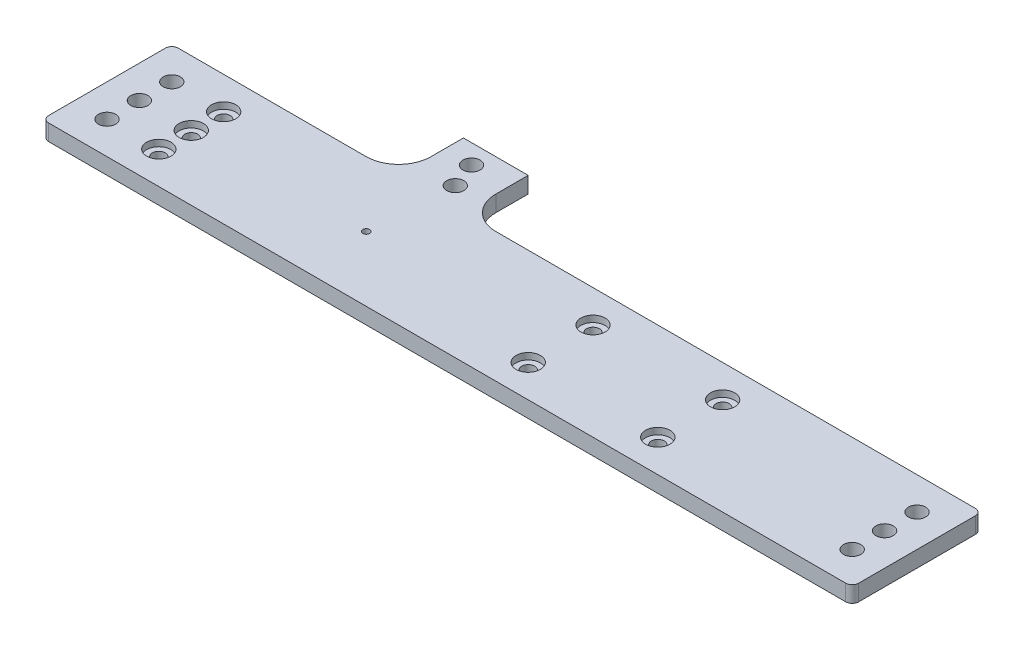
SolidWorks part; units mm, degrees
material "6061-T6 (SS)"
ref_plane "Front" through (0, 0, 0) normal (0, 0, 1) x (1, 0, 0)
ref_plane "Top" through (0, 0, 0) normal (0, 1, 0) x (1, 0, 0)
ref_plane "Right" through (0, 0, 0) normal (1, 0, 0) x (0, 0, -1)
sketch "Sketch1" plane through (0, 0, 0) normal (0, 1, 0) x (1, 0, 0)
  line L1 (-158.75, -25.4) -> (158.75, -25.4)
  line L2 (-158.75, -25.4) -> (-158.75, 25.4)
  line L3 (-158.75, 25.4) -> (158.75, 25.4)
  line L4 (158.75, -25.4) -> (158.75, 25.4)
  line L5 (-158.75, -25.4) -> (158.75, 25.4) construction
  line L6 (-158.75, 25.4) -> (158.75, -25.4) construction
  point P0 (0, 0)
  dimension "D1" = 50.8
  dimension "D2" = 317.5
extrude "Boss-Extrude1" add sketch "Sketch1" along normal blind 6.35
hole_wizard "CBORE for #10 Socket Head Cap Screw1" positions "Sketch2" profile "Sketch4" counterbore size "#10" standard "ANSI Inch" end condition through all
sketch "Sketch2" plane through (0, 6.35, 0) normal (0, 1, 0) x (1, 0, 0)
  line L2 (158.75, 25.4) -> (-158.75, 25.4) construction
  line L6 (-158.75, -25.4) -> (158.75, -25.4) construction
  line L8 (-158.75, 25.4) -> (-158.75, -25.4) construction
  line L12 (158.75, -25.4) -> (158.75, 25.4) construction
  line L15 (19.05, 12.7) -> (19.05, 25.4) construction
  line L17 (19.05, -12.7) -> (19.05, -25.4) construction
  line L18 (-125.73, -25.4) -> (-125.73, -12.7) construction
  line L20 (-125.73, 0) -> (-125.73, 12.7) construction
  line L21 (-125.73, 12.7) -> (-125.73, 25.4) construction
  line L22 (-125.73, 0) -> (-125.73, -12.7) construction
  point P64 (19.05, 12.7)
  point P66 (69.85, 12.7)
  point P68 (19.05, -12.7)
  point P70 (69.85, -12.7)
  point P92 (-125.73, 12.7)
  point P94 (-125.73, 0)
  point P102 (-125.73, -12.7)
  dimension "D2" = 50.8
  dimension "D3" = 25.4
  dimension "D4" = 88.9
  dimension "D5" = 33.02
sketch "Sketch4" plane through (-125.73, 6.35, 12.7) normal (1, 0, 0) x (0, 0, 1)
  line L0 (0, 0) -> (0, 6.35)
  line L1 (0, 6.35) -> (2.5527, 6.35)
  line L3 (2.5527, 6.35) -> (2.5527, 2.54)
  line L4 (2.5527, 2.54) -> (4.7625, 2.54)
  line L5 (4.7625, 2.54) -> (4.7625, 0)
  line L7 (4.7625, 0) -> (0, 0)
  line L11 (0, -6.35) -> (0, 107.95) construction
  dimension "Thru Hole Dia." = 5.1054
  dimension "Thru Hole Depth" = 6.35
  dimension "C'Bore Dia." = 9.525
  dimension "C'Bore Depth" = 2.54
sketch "Sketch7" plane through (0, 0, 0) normal (0, -1, 0) x (1, 0, 0)
  line L0 (-146.05, 25.4) -> (-146.05, 12.7) construction
  line L1 (-158.75, 25.4) -> (158.75, 25.4) construction
  line L2 (-146.05, 12.7) -> (-146.05, 0) construction
  line L3 (-146.05, 0) -> (-146.05, -12.7) construction
  line L4 (-146.05, -12.7) -> (-146.05, -25.4) construction
  line L5 (158.75, -25.4) -> (-158.75, -25.4) construction
  line L7 (-158.75, -25.4) -> (-158.75, 25.4) construction
  line L8 (146.05, 25.4) -> (146.05, 12.7) construction
  line L9 (146.05, 12.7) -> (146.05, 0) construction
  line L10 (146.05, 0) -> (146.05, -12.7) construction
  line L11 (146.05, -12.7) -> (146.05, -25.4) construction
  line L13 (158.75, 25.4) -> (158.75, -25.4) construction
  point P0 (-146.05, 12.7)
  point P2 (-146.05, 0)
  point P4 (-146.05, -12.7)
  point P6 (146.05, 12.7)
  point P8 (146.05, 0)
  point P10 (146.05, -12.7)
  dimension "D1" = 12.7
  dimension "D2" = 12.7
hole_wizard "1/4 Clearance Hole2" positions "Sketch7" profile "Sketch6" hole size "1/4" standard "ANSI Inch" end condition through all
sketch "Sketch6" plane through (-146.05, 0, 12.7) normal (1, 0, 0) x (0, 0, -1)
  line L0 (0, 0) -> (0, 6.35)
  line L1 (0, 6.35) -> (3.3782, 6.35)
  line L2 (3.3782, 6.35) -> (3.3782, 0)
  line L5 (3.3782, 0) -> (0, 0)
  line L11 (0, -6.35) -> (0, 107.95) construction
  dimension "Thru Hole Dia." = 6.7564
  dimension "Thru Hole Depth" = 6.35
sketch "Sketch10" plane through (0, 0, 0) normal (0, -1, 0) x (-1, 0, 0)
  line L0 (158.75, 25.4) -> (158.75, -25.4) construction
  point P0 (57.15, 0)
  dimension "D1" = 101.6
hole_wizard "#6-32 Tapped Hole1" positions "Sketch10" profile "Sketch9" tap size "#6-32" standard "ANSI Inch" end condition through all
sketch "Sketch9" plane through (-57.15, 0, 0) normal (1, 0, 0) x (0, 0, -1)
  line L0 (0, 0) -> (0, 6.35)
  line L1 (0, 6.35) -> (1.3525, 6.35)
  line L2 (1.3525, 6.35) -> (1.3525, 0)
  line L5 (1.3525, 0) -> (0, 0)
  line L11 (0, -6.35) -> (0, 107.95) construction
  dimension "Thru Tap Drill Dia." = 2.7051
  dimension "Thru Tap Drill Depth" = 6.35
cosmetic thread "Hole Thread1" parameters "D2"=3.5052
sketch "Sketch11" plane through (0, 0, 0) normal (0, -1, 0) x (1, 0, 0)
  line L0 (158.75, -25.4) -> (-158.75, -25.4) construction
  line L1 (-70.0118, -25.4) -> (-48.1024, -25.4)
  line L2 (-70.0118, -25.4) -> (-70.0118, -45.81)
  line L3 (-70.0118, -45.81) -> (-48.1024, -45.81)
  line L4 (-48.1024, -25.4) -> (-48.1024, -45.81)
extrude "Boss-Extrude2" [suppressed] add sketch "Sketch11" against normal up to surface (6.35 mm away) up to face at (-57.15, 6.35, -1.3526)
sketch "Sketch12" plane through (0, 6.35, 0) normal (0, 1, 0) x (1, 0, 0)
  line L5 (-158.75, 25.4) -> (-158.75, -25.4) construction
  line L6 (-69.85, 25.4) -> (-69.85, 50.8)
  line L7 (158.75, 25.4) -> (-158.75, 25.4) construction
  line L8 (-69.85, 50.8) -> (-44.45, 50.8)
  line L9 (-44.45, 50.8) -> (-44.45, 25.4)
  line L10 (-69.85, 25.4) -> (-44.45, 25.4)
  dimension "D4" = 88.9
  dimension "D5" = 25.4
  dimension "D6" = 25.4
extrude "Boss-Extrude3" add sketch "Sketch12" against normal up to surface (6.35 mm away) up to face at (-57.15, 0, -1.3526)
sketch "Sketch15" plane through (0, 0, 0) normal (0, -1, 0) x (-1, 0, 0)
  point P0 (59.055, 43.18)
  point P3 (55.245, 33.02)
hole_wizard "1/4 Clearance Hole1" positions "Sketch15" profile "Sketch14" hole size "1/4" standard "ANSI Inch" end condition through all
sketch "Sketch14" plane through (-59.055, 0, -43.18) normal (1, 0, 0) x (0, 0, -1)
  line L0 (0, 0) -> (0, 6.35)
  line L1 (0, 6.35) -> (3.3782, 6.35)
  line L2 (3.3782, 6.35) -> (3.3782, 0)
  line L5 (3.3782, 0) -> (0, 0)
  line L11 (0, -6.35) -> (0, 107.95) construction
  dimension "Thru Hole Dia." = 6.7564
  dimension "Thru Hole Depth" = 6.35
fillet "Fillet1" radius 12.7 2 edges at (-44.45, 3.175, -25.4) (-69.85, 3.175, -25.4)
fillet "Fillet2" radius 2.54 4 edges at (158.75, 3.175, -25.4) (158.75, 3.175, 25.4) (-158.75, 3.175, 25.4) (-158.75, 3.175, -25.4)
